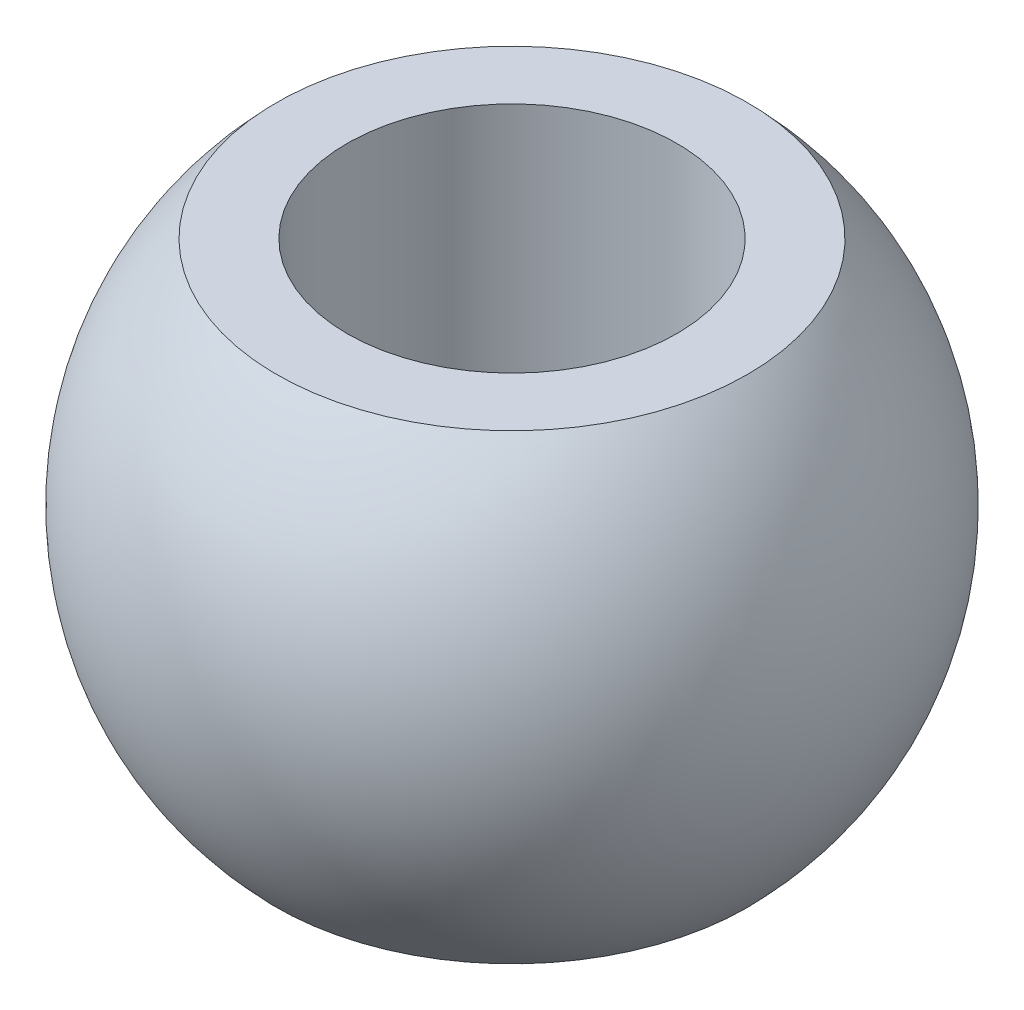
SolidWorks part; units mm, degrees
ref_plane "Front Plane" through (0, 0, 0) normal (0, 0, 1) x (1, 0, 0)
ref_plane "Top Plane" through (0, 0, 0) normal (0, 1, 0) x (1, 0, 0)
ref_plane "Right Plane" through (0, 0, 0) normal (1, 0, 0) x (0, 0, -1)
sketch "Sketch2" plane through (0, 0, 0) normal (0, 0, 1) x (1, 0, 0)
  line L0 (0, 29.8369) -> (0, -21.6847) construction
  line L1 (-33.2426, 0) -> (28.8458, 0) construction
  line L2 (5, -7) -> (5, 7)
  line L3 (5, 7) -> (7.1414, 7)
  line L4 (5, -7) -> (7.1414, -7)
  line L5 (-5, -7) -> (-5, 7) construction
  arc A0 (7.1414, 7) -> (7.1414, -7) centre (0, 0) cw
  point P11 (5, 0)
  dimension "D1" = 10
  dimension "D2" = 14
  dimension "D3" = 10
revolve "Revolve1" add sketch "Sketch2" angle 360 about L0
ref_axis "Axis1" through (0, -7, 0) along (0, 1, 0)
